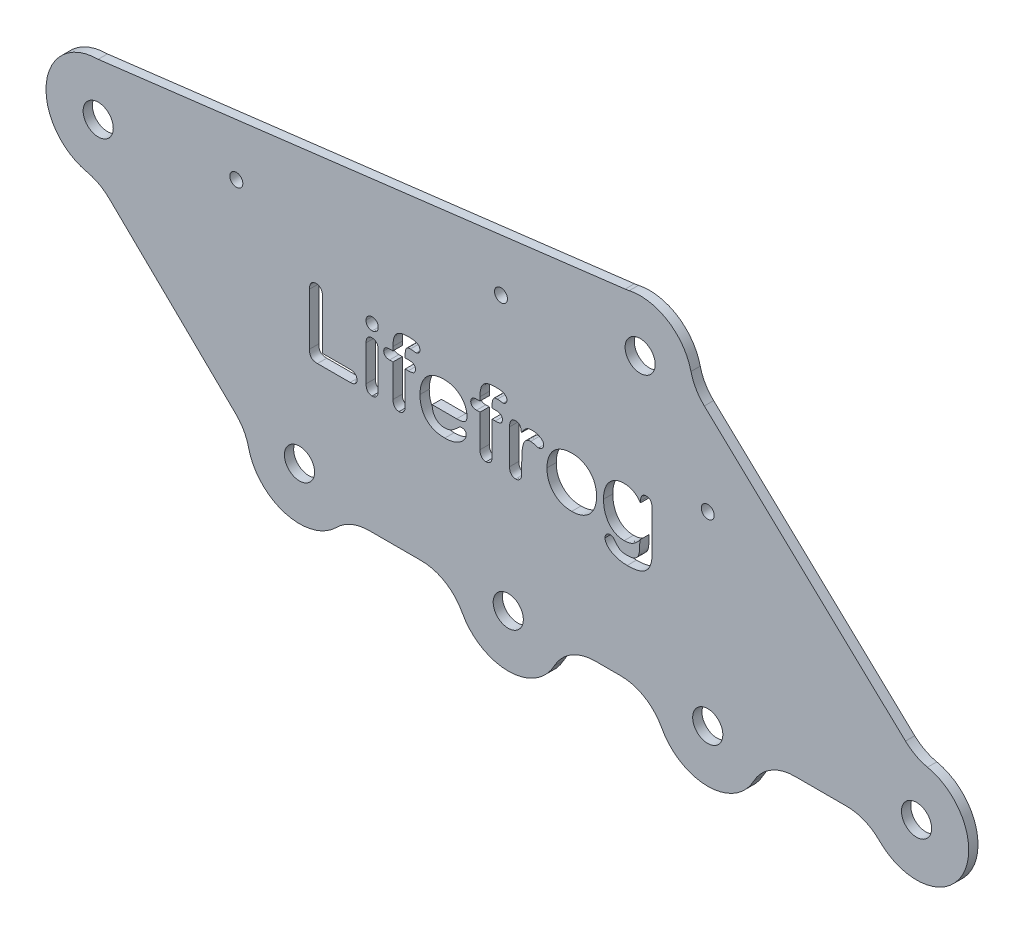
SolidWorks part; units mm, degrees
ref_plane "Front Plane" through (0, 0, 0) normal (0, 0, 1) x (1, 0, 0)
ref_plane "Top Plane" through (0, 0, 0) normal (0, 1, 0) x (1, 0, 0)
ref_plane "Right Plane" through (0, 0, 0) normal (1, 0, 0) x (0, 0, -1)
sketch "Sketch2" plane through (0, 0, 0) normal (0, 0, 1) x (1, 0, 0)
  line L0 (-96.303, -40.0195) -> (103.697, -40.0195) construction
  line L1 (56.1417, 22.4699) -> (-25.9295, 22.4699) construction
  line L2 (56.1417, 22.4699) -> (56.1417, -53.9544) construction
  line L3 (56.1417, -53.9544) -> (-159.2025, -53.9544) construction
  line L4 (-159.2025, 22.4699) -> (-159.2025, -53.9544) construction
  line L5 (-96.303, -40.0195) -> (-53.2713, -40.0195) construction
  line L6 (-96.303, -47.5195) -> (-96.303, -60.0195) construction
  line L7 (-96.303, -60.0195) -> (73.7025, -60.0195) construction
  line L8 (-96.303, -60.0195) -> (-302.9325, -60.0195) construction
  line L9 (-62.0853, -60.0195) -> (-73.2496, -62.9155) construction
  line L10 (-19.0853, -47.5195) -> (-15.8353, -47.5195) construction
  line L11 (25.9147, -47.5195) -> (25.9147, -41.2921) construction
  line L12 (-62.0853, -47.5195) -> (-107.0853, -47.5195) construction
  line L13 (-107.0853, -47.5195) -> (-107.0853, -42.5195) construction
  line L14 (-62.0853, -47.5195) -> (-58.8353, -47.5195) construction
  line L15 (-167.9726, 0) -> (-124.5853, -42.5195) construction
  line L16 (-124.5853, -42.5195) -> (-167.9726, -42.9578) construction
  line L17 (-167.9726, -42.9578) -> (-167.9726, 0) construction
  line L18 (-167.9726, -42.9578) -> (-167.9726, -60.0195) construction
  line L19 (-148.0731, -13.5847) -> (-120.8252, -40.0968)
  line L21 (-150.4726, 11.25) -> (-36.8786, 25.1494)
  line L24 (-19.8262, 11.8603) -> (23.5313, -29.0221)
  line L25 (11.3122, -40.0195) -> (103.697, -40.0195) construction
  line L26 (-41.384, 22.4699) -> (-159.2025, 22.4699) construction
  line L27 (-43.3353, -47.5195) -> (-37.8353, -47.5195)
  line L28 (-0.3353, -47.5195) -> (10.8627, -47.5195)
  line L29 (-80.8353, -47.5195) -> (-92.0333, -47.5195)
  line L30 (-50.8353, -47.5195) -> (-19.0853, -47.5195) construction
  line L31 (-7.8353, -47.5195) -> (25.9147, -47.5195) construction
  line L32 (-150.4726, 0) -> (-33.6568, 14.2936) construction
  arc A0 (-21.208, 13.1632) -> (-43.1118, 22.4699) centre (-33.6568, 14.2936) ccw construction
  circle A1 centre (-33.6568, 14.2936) radius 3.25 construction
  arc A2 (-74.5853, -47.5195) -> (-51.3689, -53.9544) centre (-62.0853, -47.5195) ccw construction
  circle A3 centre (-62.0853, -47.5195) radius 3.25 construction
  circle A4 centre (25.9147, -42.5195) radius 3.25
  circle A5 centre (-19.0853, -47.5195) radius 3.25 construction
  circle A6 centre (25.9147, -42.5195) radius 17.5 construction
  circle A7 centre (25.9147, -42.5195) radius 3.25 construction
  circle A8 centre (-107.0853, -42.5195) radius 17.5 construction
  circle A9 centre (-107.0853, -42.5195) radius 3.25 construction
  circle A10 centre (-150.4726, 0) radius 17.5 construction
  circle A11 centre (-150.4726, 0) radius 3.25 construction
  arc A12 (-150.4726, 11.25) -> (-152.8942, -10.9863) centre (-150.4726, 0) ccw
  arc A13 (-118.0513, -45.0313) -> (-99.1166, -50.4607) centre (-107.0853, -42.5195) ccw
  arc A14 (-22.7028, 16.8572) -> (-36.0054, 25.2957) centre (-33.6568, 14.2936) ccw
  arc A15 (-72.0118, -52.8136) -> (-52.1588, -52.8136) centre (-62.0853, -47.5195) ccw
  arc A16 (-29.0118, -52.8136) -> (-9.1588, -52.8136) centre (-19.0853, -47.5195) ccw
  arc A17 (17.946, -50.4607) -> (28.2849, -31.522) centre (25.9147, -42.5195) ccw
  arc A18 (-7.6288, -42.5195) -> (-9.0853, -40.0195) centre (-19.0853, -47.5195) ccw construction
  arc A19 (-31.5853, -47.5195) -> (-8.3689, -53.9544) centre (-19.0853, -47.5195) ccw construction
  circle A20 centre (-19.0853, -47.5195) radius 3.25
  circle A21 centre (-62.0853, -47.5195) radius 3.25
  circle A22 centre (-107.0853, -42.5195) radius 3.25
  circle A23 centre (-150.4726, 0) radius 3.25
  circle A24 centre (-33.6568, 14.2936) radius 3.25
  arc A25 (10.8627, -47.5195) -> (17.946, -50.4607) centre (10.8627, -57.5195) cw
  arc A26 (-148.0731, -13.5847) -> (-152.8942, -10.9863) centre (-155.0468, -20.7519) ccw
  arc A27 (-120.8252, -40.0968) -> (-118.0513, -45.0313) centre (-127.7989, -47.264) cw
  arc A28 (-92.0333, -47.5195) -> (-99.1166, -50.4607) centre (-92.0333, -57.5195) ccw
  arc A29 (-80.8353, -47.5195) -> (-72.0118, -52.8136) centre (-80.8353, -57.5195) cw
  arc A30 (-37.8353, -47.5195) -> (-29.0118, -52.8136) centre (-37.8353, -57.5195) cw
  arc A31 (-43.3353, -47.5195) -> (-52.1588, -52.8136) centre (-43.3353, -57.5195) ccw
  arc A32 (-36.0054, 25.2957) -> (-36.8786, 25.1494) centre (-38.0931, 35.0753) cw
  arc A33 (-19.8262, 11.8603) -> (-22.7028, 16.8572) centre (-12.9659, 19.136) cw
  arc A34 (23.5313, -29.0221) -> (28.2849, -31.522) centre (30.3916, -21.7464) ccw
  arc A35 (-0.3353, -47.5195) -> (-9.1588, -52.8136) centre (-0.3353, -57.5195) ccw
  point P67 (15.8369, -47.5195)
  point P70 (-150.4726, -11.25)
  point P73 (-118.3353, -42.5195)
  point P76 (-97.0075, -47.5195)
  point P79 (-73.3353, -47.5195)
  point P82 (-30.3353, -47.5195)
  point P91 (-22.4068, 14.2936)
  point P94 (25.9147, -31.2695)
  dimension "D1" = 25
  dimension "D2" = 6.5
  dimension "D5" = 35
  dimension "D6" = 6.5
  dimension "D10" = 22.5
  dimension "D11" = 22.5
  dimension "D12" = 22.5
  dimension "D13" = 6.5
  dimension "D14" = 6.5
  dimension "D15" = 22.5
  dimension "D16" = 22.5
  dimension "D17" = 22.5
  dimension "D18" = 10
  dimension "D19" = 10
  dimension "D3" = 20
  dimension "D4" = 0
  dimension "D7" = 45
  dimension "D8" = 43
  dimension "D9" = 45
extrude "Boss-Extrude1" add sketch "Sketch2" along normal blind 2
sketch "Sketch5" plane through (0, 0, 2) normal (0, 0, 1) x (1, 0, 0)
  line L1 (-106.4284, -21.9146) -> (-30.7738, -21.9146) construction
  line L2 (-106.4284, -21.9146) -> (-106.4284, -6.1743) construction
  line L3 (-106.4284, -6.1743) -> (-30.7738, -6.1743) construction
  line L4 (-30.7738, -21.9146) -> (-30.7738, -6.1743) construction
  text T0 "Lifefrog" font "Arial Rounded MT Bold" height 15
  point P5 (0, 0)
  point P6 (-107.6738, -21.9146)
sketch "Sketch7" plane through (0, 0, 2) normal (0, 0, 1) x (1, 0, 0)
  line L0 (-150.4726, 0) -> (-33.6568, 14.2936) construction
  line L1 (-150.4726, 0) -> (-107.0853, -42.5195) construction
  line L2 (-107.0853, -42.5195) -> (25.9147, -42.5195) construction
  line L3 (25.9147, -42.5195) -> (-33.6568, 14.2936) construction
  line L5 (-107.0853, -2.5195) -> (-35.0853, -2.5195) construction
  line L6 (25.9147, -42.5195) -> (25.9147, -7.5195) construction
  line L7 (25.9147, -7.5195) -> (-64.0853, -7.5195) construction
  circle A0 centre (-120.6947, 3.6436) radius 1.4
  circle A1 centre (-63.6568, 10.6228) radius 1.4
  circle A5 centre (-19.0853, -7.5195) radius 1.4
  dimension "D1" = 2.8
  dimension "D2" = 2.8
  dimension "D4" = 30
  dimension "D5" = 2.8
  dimension "D6" = 40
  dimension "D3" = 30
  dimension "D7" = 35
  dimension "D9" = 45
extrude "Cut-Extrude4" cut sketch "Sketch7" against normal through all
extrude "Cut-Extrude5" cut sketch "Sketch5" against normal through all both and the other way through all
sketch "Sketch8" plane through (0, 0, 2) normal (0, 0, 1) x (1, 0, 0)
  line L0 (-77.9803, -14.6107) -> (-74.1611, -14.6107) construction
  line L1 (-77.9803, -12.7041) -> (-74.1611, -12.7041)
  line L2 (-77.9803, -16.5174) -> (-74.1611, -16.5174)
  arc A0 (-77.9803, -12.7041) -> (-77.9803, -16.5174) centre (-77.9803, -14.6107) ccw
  arc A1 (-74.1611, -16.5174) -> (-74.1611, -12.7041) centre (-74.1611, -14.6107) ccw
  circle A2 centre (-48.4705, -16.5174) radius 4.12
  circle A3 centre (-36.433, -16.5174) radius 3.6209
  point P2 (-76.0707, -14.6107)
extrude "Cut-Extrude6" cut sketch "Sketch8" against normal blind 10
